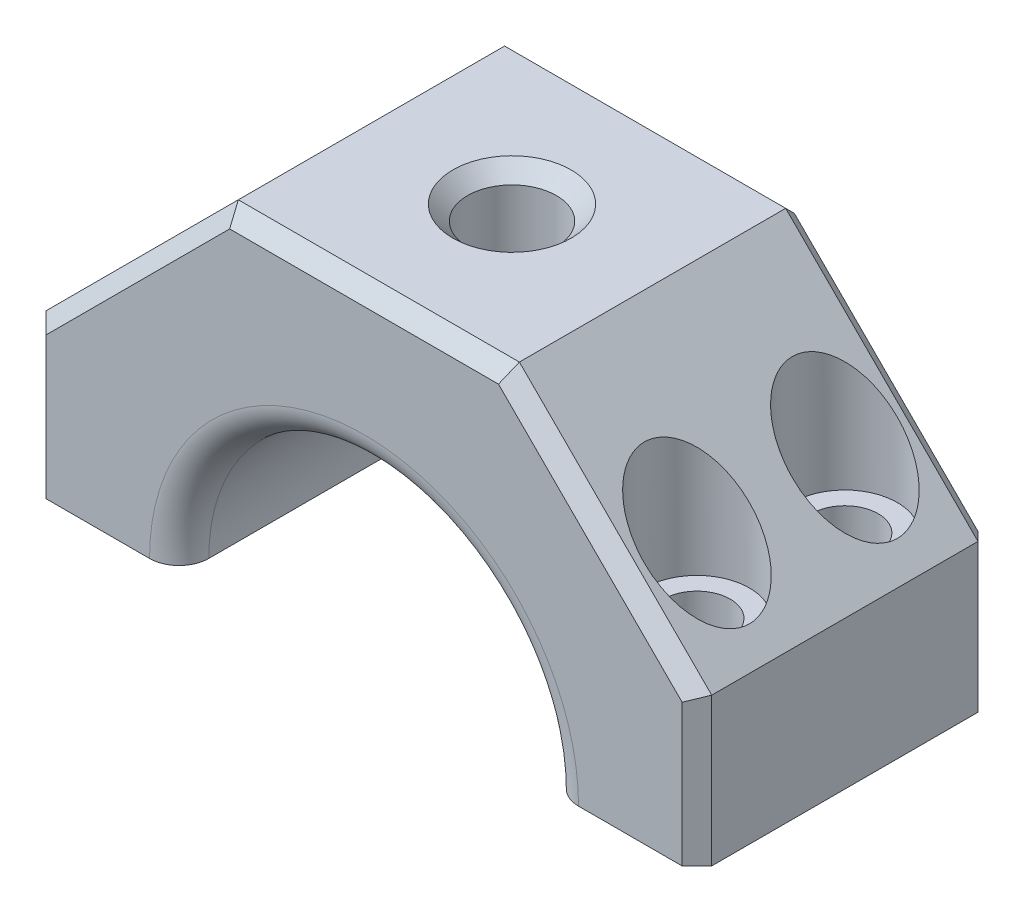
SolidWorks part; units mm, degrees
ref_plane "Front Plane" through (0, 0, 0) normal (0, 0, 1) x (1, 0, 0)
ref_plane "Top Plane" through (0, 0, 0) normal (0, 1, 0) x (1, 0, 0)
ref_plane "Right Plane" through (0, 0, 0) normal (1, 0, 0) x (0, 0, -1)
sketch "Sketch1" plane through (0, 0, 0) normal (0, 1, 0) x (1, 0, 0)
  line L0 (0, -10) -> (0, 10) construction
  line L1 (-22.5, 0) -> (22.5, 0) construction
  line L2 (0, 10) -> (-22.5, 10)
  line L3 (-22.5, 10) -> (-22.5, -10)
  line L4 (-22.5, -10) -> (22.5, -10)
  line L5 (22.5, -10) -> (22.5, 10)
  line L6 (22.5, 10) -> (0, 10)
  point P4 (0, 0)
  point P8 (0, 0)
  dimension "D1" = 45
  dimension "D2" = 20
extrude "Boss-Extrude1" add sketch "Sketch1" along normal blind 23
ref_plane "Plane1" through (0, 0, 10) normal (0, 0, 1) x (1, 0, 0)
sketch "Sketch2" plane through (0, 0, 10) normal (0, 0, 1) x (1, 0, 0)
  line L0 (-22.5, 0) -> (22.5, 0) construction
  line L1 (-12.5, 0) -> (-22.5, 0)
  line L2 (-22.5, 0) -> (-22.5, -2.5226)
  line L3 (-22.5, -2.5226) -> (22.5, -2.5226)
  line L4 (22.5, -2.5226) -> (22.5, 0)
  line L5 (22.5, 0) -> (12.5, 0)
  circle A0 centre (0, 0) radius 12.5 construction
  arc A1 (-12.5, 0) -> (12.5, 0) centre (0, 0) cw
  dimension "D1" = 25
extrude "Cut-Extrude1" cut sketch "Sketch2" against normal up to next
sketch "Sketch3" plane through (0, 0, 0) normal (0, 1, 0) x (1, 0, 0)
  line L0 (-12.5, 10) -> (-12.5, 0) construction
  line L1 (-12.5, -10) -> (-12.5, 10) construction
  line L2 (-12.5, 0) -> (-22.5, 0) construction
  line L3 (-22.5, 10) -> (-22.5, -10) construction
  line L4 (-17.5, 0) -> (-17.5, -5) construction
  line L5 (-17.5, 0) -> (-17.5, 5) construction
  circle A0 centre (-17.5, -5) radius 2.25
  circle A1 centre (-17.5, 5) radius 2.25
  dimension "D1" = 4.5
  dimension "D2" = 4.5
extrude "Cut-Extrude2" cut sketch "Sketch3" along normal up to next
mirror "Mirror1" about plane through (0, 0, 0) normal (1, 0, 0) of "Cut-Extrude2"
sketch "Sketch4" plane through (0, 0, 0) normal (0, 1, 0) x (1, 0, 0)
  circle A0 centre (-17.5, 5) radius 3.55
  circle A1 centre (-17.5, -5) radius 3.55
  dimension "D1" = 7.1
  dimension "D2" = 7.1
extrude "Cut-Extrude3" cut sketch "Sketch4" against normal blind 13 from offset 23
mirror "Mirror2" about plane through (0, 0, 0) normal (1, 0, 0) of "Cut-Extrude3"
fillet "Fillet1" radius 2 2 edges at (0, 12.5, -10) (0, 12.5, 10)
chamfer "Chamfer1" distance 13 2 edges at (22.5, 23, 0) (-22.5, 23, 0)
chamfer "Chamfer2" distance 1 10 edges at (22.5, 5, 10) (16, 16.5, 10) (0, 23, 10) (-16, 16.5, 10) (-22.5, 5, 10) (22.5, 5, -10) (16, 16.5, -10) (0, 23, -10) (-16, 16.5, -10) (-22.5, 5, -10)
ref_plane "Plane2" through (0, 23, 0) normal (0, 1, 0) x (1, 0, 0)
sketch "Sketch5" plane through (0, 23, 0) normal (0, 1, 0) x (1, 0, 0)
  circle A0 centre (0, 0) radius 3
  dimension "D1" = 6
extrude "Cut-Extrude4" cut sketch "Sketch5" against normal up to next
chamfer "Chamfer3" distance 1 angle 45 1 edges at (0, 23, 3)
